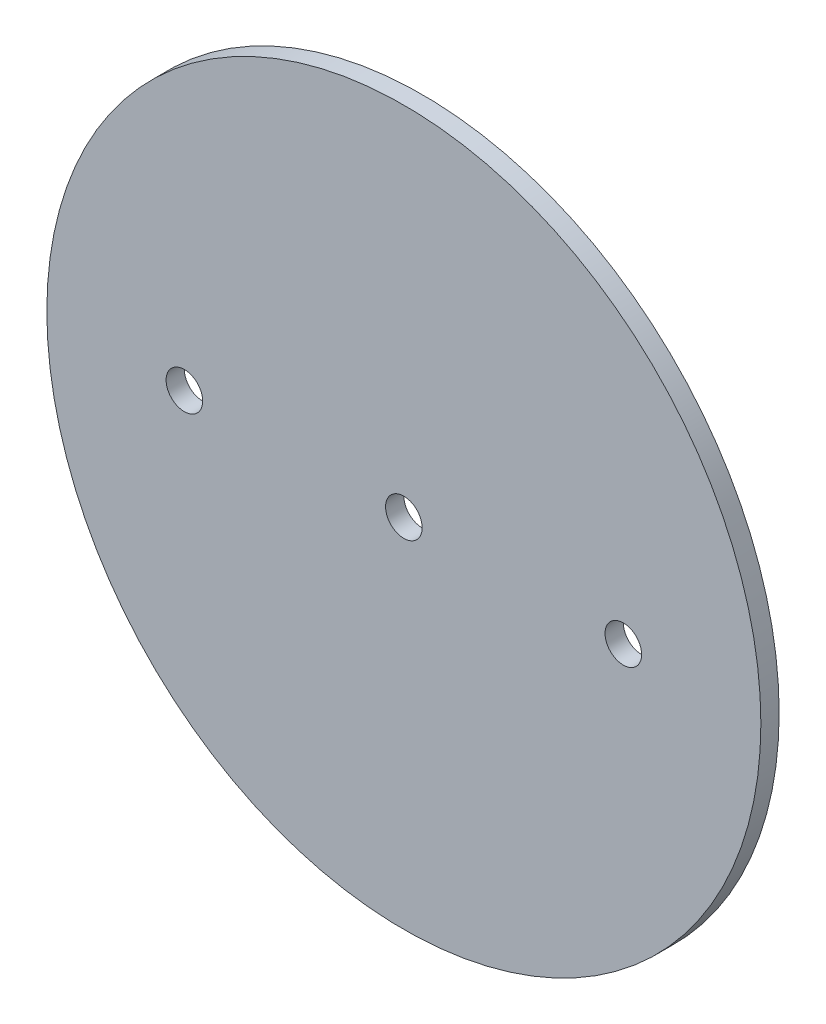
SolidWorks part; units mm, degrees
ref_plane "Front Plane" through (0, 0, 0) normal (0, 0, 1) x (1, 0, 0)
ref_plane "Top Plane" through (0, 0, 0) normal (0, 1, 0) x (1, 0, 0)
ref_plane "Right Plane" through (0, 0, 0) normal (1, 0, 0) x (0, 0, -1)
sketch "Sketch1" plane through (0, 0, 0) normal (0, 0, 1) x (1, 0, 0)
  circle A0 centre (0, 0) radius 61.976
  dimension "D1" = 123.952
extrude "Boss-Extrude1" add sketch "Sketch1" along normal mid plane 3.175
sketch "Sketch2" plane through (0, 0, 1.5875) normal (0, 0, 1) x (1, 0, 0)
  line L0 (-1000, 0) -> (49000, 0) construction
  point P1 (0, 0)
  point P4 (38.1, 0)
  point P5 (-38.1, 0)
  dimension "D1" = 38.1
  dimension "D2" = 76.2
hole_wizard "1/4 (0.25) Diameter Hole1" positions "Sketch2" profile "Sketch3" hole size "1/4" standard "ANSI Inch" end condition through all
sketch "Sketch3" plane through (-38.1, 0, 1.5875) normal (1, 0, 0) x (0, -1, 0)
  line L0 (0, 0) -> (0, 3.175)
  line L1 (0, 3.175) -> (3.175, 3.175)
  line L2 (3.175, 3.175) -> (3.175, 0)
  line L5 (3.175, 0) -> (0, 0)
  line L11 (0, -6.35) -> (0, 107.95) construction
  dimension "Thru Hole Dia." = 6.35
  dimension "Thru Hole Depth" = 3.175
equation "\"AIRFRAME_OD\"= 5.15in"
equation "\"AIRFRAME_ID\"= 5.00in"
equation "\"FLAT_T\"= 0.125in"
equation "\"NOSE_EXP_L\"= 27in"
equation "\"NOSE_SHOULDER_L\"= 5in"
equation "\"MAIN_L\"= 30in"
equation "\"RECO_COUP_L\"= 10in"
equation "\"RECO_SWITCH_L\"= 2in"
equation "\"DROGUE_L\"= 20in"
equation "\"ATS_FORE_COUP_L\"= 5.5in"
equation "\"ATS_AFT_COUP_L\"= 4.5in"
equation "\"LOWER_L\"= 30in"
equation "\"FIN_N\"= 4"
equation "\"CR_AFT_X\"= 0.5in"
equation "\"CR_FORE_X\"= 9.25in"
equation "\"FIN_ROOT\"= 8in"
equation "\"FIN_X\"= 0.75in"
equation "\"MOTOR_OD\"= 3.091in"
equation "\"MOTOR_ID\"= 3.00in"
equation "\"COUPLER_OD\"= 4.998in"
equation "\"COUPLER_ID\"= 4.88in"
equation "\"D1@Sketch1\"=\"COUPLER_ID\""
equation "\"D1@Boss-Extrude1\"=\"FLAT_T\""
equation "\"RECO_ROD_X\"= 3.5in"
equation "\"ATS_ROD_X\"= 3in"
equation "\"D1@Sketch2\"=\"ATS_ROD_X\"*0.5"
equation "\"D2@Sketch2\"=\"ATS_ROD_X\""
equation "\"MOTOR_L\"= 14in"
equation "\"MOTOR_LOWER_X\"= 2in"
